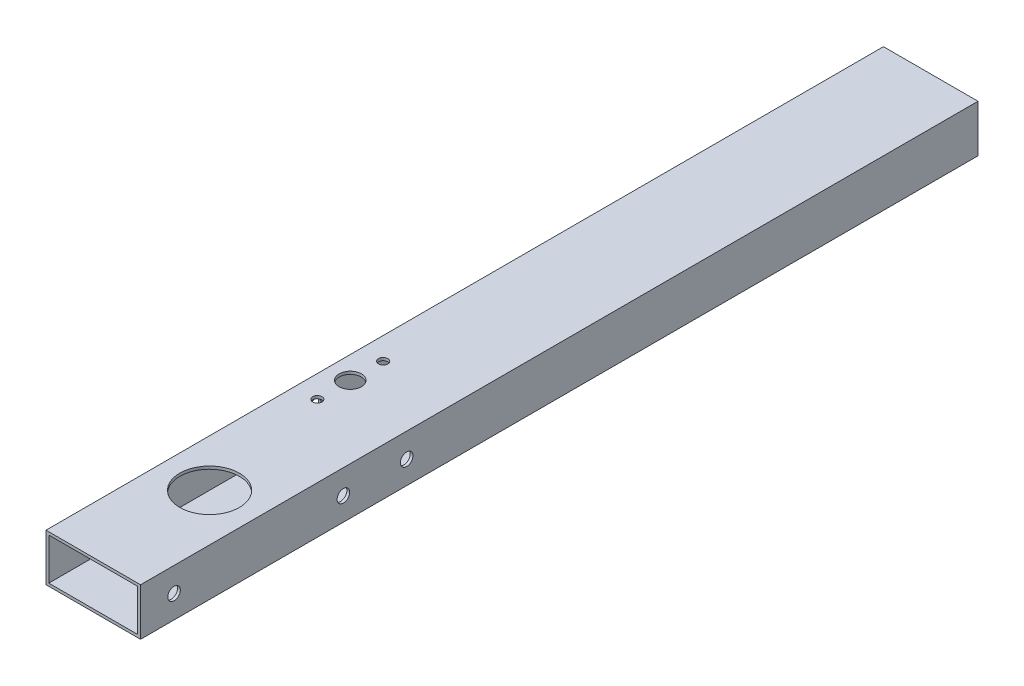
SolidWorks part; units mm, degrees
material "AISI 1015 Acero estirado en frío (SS)"
ref_plane "Alzado" through (0, 0, 0) normal (0, 0, 1) x (1, 0, 0)
ref_plane "Planta" through (0, 0, 0) normal (0, 1, 0) x (1, 0, 0)
ref_plane "Vista lateral" through (0, 0, 0) normal (1, 0, 0) x (0, 0, -1)
sketch "Croquis1" plane through (0, 0, 0) normal (0, 0, 1) x (1, 0, 0)
  line L0 (-23.9, 11.2) -> (23.9, 11.2)
  line L1 (-25.4, -12.7) -> (25.4, -12.7)
  line L2 (-25.4, -12.7) -> (-25.4, 12.7)
  line L3 (-25.4, 12.7) -> (25.4, 12.7)
  line L4 (25.4, -12.7) -> (25.4, 12.7)
  line L5 (-25.4, -12.7) -> (25.4, 12.7) construction
  line L6 (-25.4, 12.7) -> (25.4, -12.7) construction
  line L7 (23.9, -11.2) -> (23.9, 11.2)
  line L8 (-23.9, -11.2) -> (23.9, -11.2)
  line L9 (-23.9, -11.2) -> (-23.9, 11.2)
  point P0 (0, 0)
  dimension "D1" = 25.4
  dimension "D2" = 50.8
  dimension "D3" = 1.5
extrude "Saliente-Extruir1" add sketch "Croquis1" along normal blind 450
ref_plane "Plano1" through (0, 12.7, 0) normal (0, 1, 0) x (1, 0, 0)
sketch "Croquis2" plane through (0, 12.7, 0) normal (0, 1, 0) x (1, 0, 0)
  line L0 (0, -450) -> (0, -262.1851) construction
  line L1 (25.4, -450) -> (-25.4, -450) construction
  line L2 (25.4, -387.5) -> (-25.7584, -387.5) construction
  line L3 (25.4, -450) -> (25.4, 0) construction
  circle A0 centre (0, -387.5) radius 16
  dimension "D2" = 32
  dimension "D1" = 62.5
extrude "Cortar-Extruir1" cut sketch "Croquis2" against normal blind 26
hole_wizard "Taladro de margen para 1/42" positions "Croquis5" profile "Croquis6" hole size "1/4" standard "Ansi Inch" end condition through all
sketch "Croquis5" plane through (-26.4, 572.4886, 162.9891) normal (-1, 0, 0) x (0, -1, 0)
  point P0 (572.8886, 269.0109)
  point P1 (572.8886, 178.0109)
  point P2 (572.8886, 144.0109)
sketch "Croquis6" plane through (-26.4, -0.4, 432) normal (0, 1, 0) x (0, 0, 1)
  line L0 (0, 0) -> (0, 51.8)
  line L1 (0, 51.8) -> (3.3782, 51.8)
  line L2 (3.3782, 51.8) -> (3.3782, 0)
  line L3 (3.3782, 0) -> (0, 0)
  line L4 (0, -6.35) -> (0, 107.95) construction
  dimension "Diámetro de taladro hasta el siguiente" = 6.7564
  dimension "Profundidad de taladro hasta el siguiente" = 51.8
sketch "Croquis7" plane through (0, 12.7, 0) normal (0, 1, 0) x (1, 0, 0)
  line L0 (25.4, -298.5) -> (-25.4, -298.5) construction
  line L1 (25.4, -450) -> (25.4, 0) construction
  line L2 (-25.4, -450) -> (-25.4, 0) construction
  line L3 (-13.4, -280.8) -> (-13.4, -316.2) construction
  circle A0 centre (-13.4, -298.5) radius 6
  circle A1 centre (-13.4, -280.8) radius 2.5
  circle A2 centre (-13.4, -316.2) radius 2.5
  point P6 (0, -387.5)
  point P11 (-13.4, -298.5)
  dimension "D4" = 5
  dimension "D5" = 12
  dimension "D1" = 89
  dimension "D2" = 12
  dimension "D3" = 35.4
extrude "Cortar-Extruir2" cut sketch "Croquis7" against normal up to surface (25.4 mm away) up to face at (0, -12.7, 403.5)
